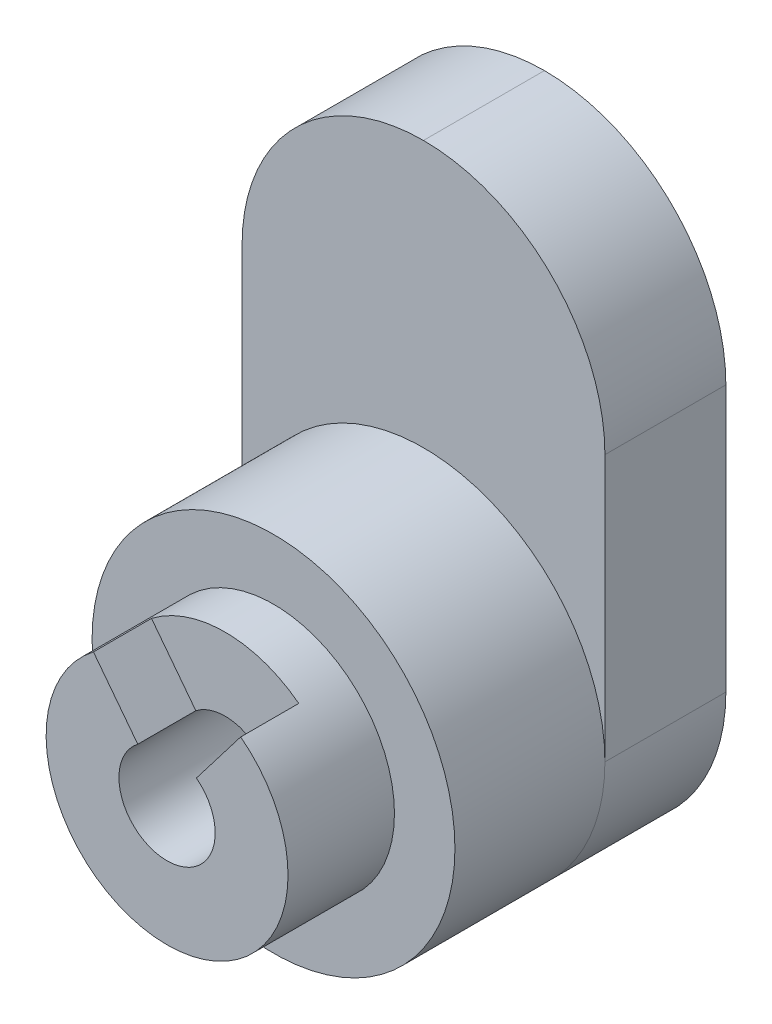
SolidWorks part; units mm, degrees
ref_plane "Front Plane" through (0, 0, 0) normal (0, 0, 1) x (1, 0, 0)
ref_plane "Top Plane" through (0, 0, 0) normal (0, 1, 0) x (1, 0, 0)
ref_plane "Right Plane" through (0, 0, 0) normal (1, 0, 0) x (0, 0, -1)
sketch "Sketch1" plane through (0, 0, 0) normal (0, 0, 1) x (1, 0, 0)
  line L1 (-9.525, 0) -> (9.525, 0)
  line L2 (-9.525, 0) -> (-9.525, 33.02)
  line L3 (-9.525, 33.02) -> (9.525, 33.02)
  line L4 (9.525, 0) -> (9.525, 33.02)
  point P4 (0, 0)
  dimension "D1" = 33.02
  dimension "D2" = 19.05
extrude "Boss-Extrude1" add sketch "Sketch1" along normal blind 6.35
sketch "Sketch2" plane through (0, 0, 6.35) normal (0, 0, 1) x (1, 0, 0)
  line L3 (-9.525, 0) -> (9.525, 0) construction
  circle A0 centre (0, 9.525) radius 6.35
  dimension "D1" = 12.7
  dimension "D2" = 9.525
extrude "Boss-Extrude2" add sketch "Sketch2" along normal blind 13.462
hole_wizard "#8 (0.199) Diameter Hole1" positions "Sketch3" profile "Sketch4" hole size "#8" standard "ANSI Inch" end condition through all
sketch "Sketch3" plane through (0, 0, 19.812) normal (0, 0, 1) x (1, 0, 0)
  circle A0 centre (0, 9.525) radius 6.35 construction
  point P0 (0, 9.525)
sketch "Sketch4" plane through (0, 9.525, 19.812) normal (1, 0, 0) x (0, -1, 0)
  line L0 (0, 0) -> (0, 19.812)
  line L1 (0, 19.812) -> (2.5273, 19.812)
  line L2 (2.5273, 19.812) -> (2.5273, 0)
  line L5 (2.5273, 0) -> (0, 0)
  line L11 (0, -6.35) -> (0, 107.95) construction
  dimension "Thru Hole Dia." = 5.0546
  dimension "Thru Hole Depth" = 19.812
sketch "Sketch5" plane through (0, 0, 0) normal (0, 0, -1) x (-1, 0, 0)
  line L1 (2.3464, 5.461) -> (4.6927, 9.525)
  line L2 (4.6927, 9.525) -> (2.3464, 13.589)
  line L3 (2.3464, 13.589) -> (-2.3464, 13.589)
  line L4 (-2.3464, 13.589) -> (-4.6927, 9.525)
  line L5 (-4.6927, 9.525) -> (-2.3464, 5.461)
  line L6 (-2.3464, 5.461) -> (2.3464, 5.461)
  circle A0 centre (0, 9.525) radius 4.064 construction
  dimension "D1" = 8.128
extrude "Cut-Extrude1" cut sketch "Sketch5" against normal blind 2.54
sketch "Sketch7" plane through (0, 0, 6.35) normal (0, 0, 1) x (1, 0, 0)
  circle A0 centre (0, 9.525) radius 9.525
  circle A1 centre (0, 9.525) radius 6.35
  circle A2 centre (0, 9.525) radius 6.35 construction
  dimension "D1" = 19.05
extrude "Boss-Extrude3" add sketch "Sketch7" along normal blind 7.874
sketch "Sketch8" plane through (0, 0, 19.812) normal (0, 0, 1) x (1, 0, 0)
  line L0 (1.5385, 11.53) -> (3.8656, 14.5628)
  line L1 (-3.8656, 14.5628) -> (-1.5385, 11.53)
  line L2 (-1.5385, 11.53) -> (0, 9.525) construction
  line L3 (0, 9.525) -> (1.5385, 11.53) construction
  arc A0 (3.8656, 14.5628) -> (-3.8656, 14.5628) centre (0, 9.525) ccw
  arc A1 (1.5385, 11.53) -> (-1.5385, 11.53) centre (0, 9.525) ccw
  circle A2 centre (0, 9.525) radius 2.5273 construction
  circle A3 centre (0, 9.525) radius 6.35 construction
  dimension "D1" = 75
extrude "Cut-Extrude2" cut sketch "Sketch8" against normal blind 3.048
fillet "Fillet1" radius 9.525 4 edges at (9.525, 0, 3.175) (-9.525, 0, 3.175) (9.525, 33.02, 3.175) (-9.525, 33.02, 3.175)
